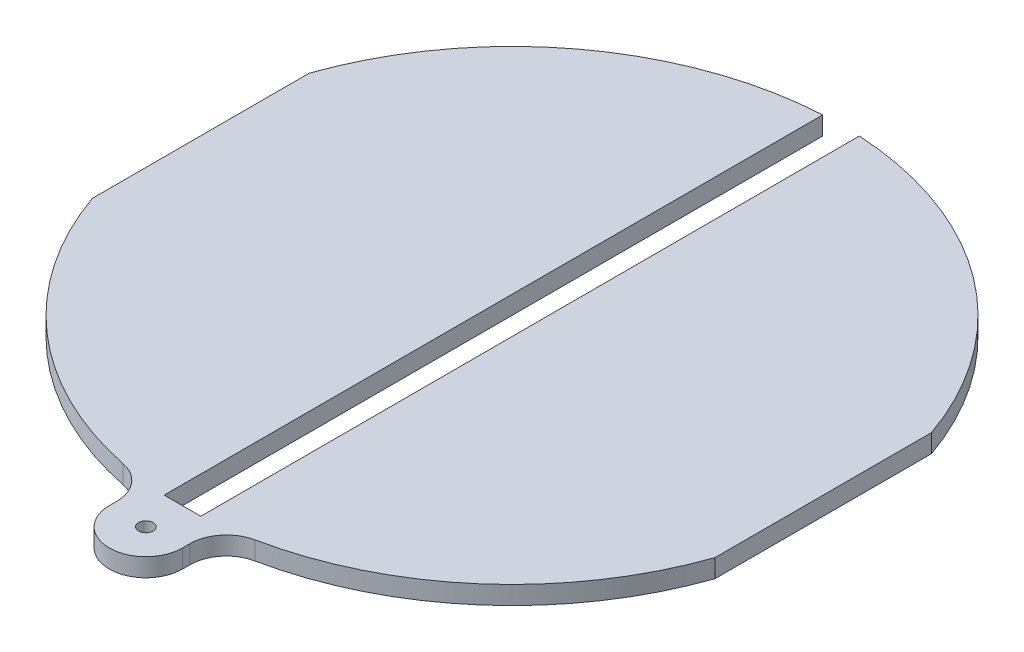
SolidWorks part; units mm, degrees
ref_plane "Front Plane" through (0, 0, 0) normal (0, 0, 1) x (1, 0, 0)
ref_plane "Top Plane" through (0, 0, 0) normal (0, 1, 0) x (1, 0, 0)
ref_plane "Right Plane" through (0, 0, 0) normal (1, 0, 0) x (0, 0, -1)
sketch "Sketch2" plane through (0, 0, 0) normal (0, 1, 0) x (1, 0, 0)
  line L0 (3.175, 60.325) -> (53.975, 60.325)
  line L1 (-53.975, -60.325) -> (-6.35, -60.325)
  line L2 (-53.975, -60.325) -> (-53.975, 60.325)
  line L3 (-53.975, 60.325) -> (-3.175, 60.325)
  line L4 (53.975, -60.325) -> (53.975, 60.325)
  line L5 (-53.975, -60.325) -> (53.975, 60.325) construction
  line L6 (-53.975, 60.325) -> (53.975, -60.325) construction
  line L7 (-3.175, -53.975) -> (3.175, -53.975)
  line L8 (-3.175, -53.975) -> (-3.175, 60.325)
  line L10 (3.175, -53.975) -> (3.175, 60.325)
  line L11 (-3.175, -53.975) -> (3.175, 60.325) construction
  line L12 (-3.175, 60.325) -> (3.175, -53.975) construction
  line L13 (6.35, -60.325) -> (53.975, -60.325)
  arc A0 (-6.35, -60.325) -> (6.35, -60.325) centre (0, -60.325) ccw
  point P0 (0, 0)
  point P6 (0, 3.175)
  dimension "D1" = 120.65
  dimension "D2" = 107.95
  dimension "D3" = 6.35
  dimension "D4" = 114.3
extrude "Boss-Extrude1" add sketch "Sketch2" along normal blind 3.175 contours L3 L8 L7 L10 L0 L4 L13 A0 L1 L2
sketch "Sketch3" plane through (0, 3.175, 0) normal (0, 1, 0) x (1, 0, 0)
  circle A0 centre (0, -60.325) radius 1.27
  dimension "D1" = 2.54
extrude "Cut-Extrude1" cut sketch "Sketch3" against normal through all
sketch "Sketch4" plane through (0, 3.175, 0) normal (0, 1, 0) x (1, 0, 0)
  line L0 (-3.175, 3.175) -> (83.1266, 3.175) construction
  line L2 (-3.175, -53.975) -> (-3.175, 60.325) construction
  line L7 (0, 0) -> (0, 96.6328) construction
  line L8 (3.175, 60.325) -> (53.975, 60.325) construction
  line L9 (-6.35, -60.325) -> (-6.35, -53.6211)
  line L10 (-53.975, 60.325) -> (53.975, 60.325)
  line L11 (-53.975, 60.325) -> (-53.975, 21.9586)
  line L12 (-53.975, -60.325) -> (-6.35, -60.325)
  line L13 (53.975, 60.325) -> (53.975, 21.9586)
  line L14 (6.35, -60.325) -> (6.35, -53.6211)
  line L15 (53.975, -15.6086) -> (53.975, -60.325)
  line L16 (-53.975, -15.6086) -> (-53.975, -60.325)
  line L17 (6.35, -60.325) -> (53.975, -60.325)
  arc A1 (-53.975, -15.6086) -> (-6.35, -53.6211) centre (0, 3.175) ccw
  arc A2 (53.975, 21.9586) -> (-53.975, 21.9586) centre (0, 3.175) ccw
  arc A3 (6.35, -53.6211) -> (53.975, -15.6086) centre (0, 3.175) ccw
  line M11 (-53.975, 60.325) -> (-53.975, -60.325)
  line M12 (-53.975, -60.325) -> (-6.35, -60.325)
  line M14 (6.35, -60.325) -> (53.975, -60.325)
  line M15 (53.975, -60.325) -> (53.975, 60.325)
  line M16 (53.975, 60.325) -> (3.175, 60.325)
  line M17 (3.175, 60.325) -> (3.175, -53.975)
  line M19 (-3.175, -53.975) -> (-3.175, 60.325)
  line M20 (-3.175, 60.325) -> (-53.975, 60.325)
extrude "Cut-Extrude2" cut sketch "Sketch4" against normal through all both and the other way through all contours A1 L9 M11 M12 | A2 M19 M20 M11 | A3 L14 M14 M15 | A2 M15 M16 M17 region at (-37.5733, 3.175, 48.3954) region at (37.5733, 3.175, 48.3954) region at (-41.542, 3.175, -50.0186) region at (41.542, 3.175, -50.0186)
fillet "Fillet1" radius 6.35 2 edges at (6.35, 1.5875, 53.6211) (-6.35, 1.5875, 53.6211)
